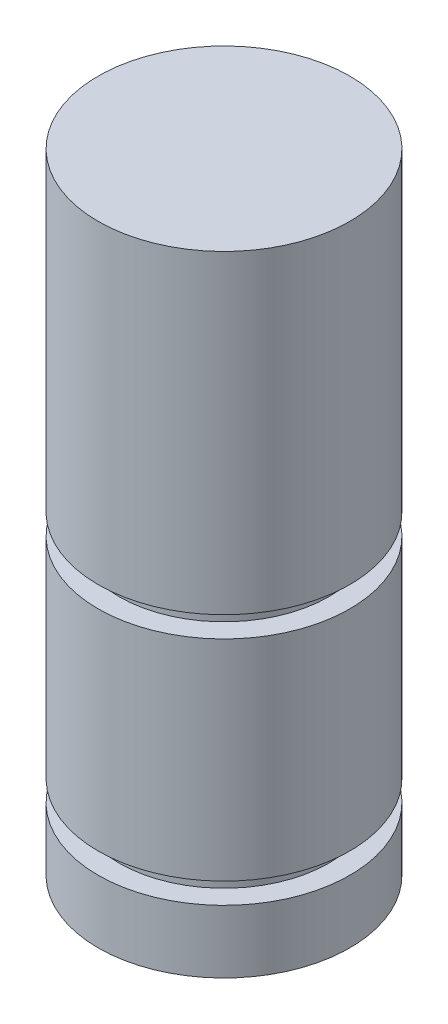
SolidWorks part; units mm, degrees
ref_plane "Front Plane" through (0, 0, 0) normal (0, 0, 1) x (1, 0, 0)
ref_plane "Top Plane" through (0, 0, 0) normal (0, 1, 0) x (1, 0, 0)
ref_plane "Right Plane" through (0, 0, 0) normal (1, 0, 0) x (0, 0, -1)
sketch "Sketch1" plane through (0, 0, 0) normal (0, 1, 0) x (1, 0, 0)
  circle A0 centre (0, 0) radius 6
  dimension "D1" = 12
extrude "Boss-Extrude1" add sketch "Sketch1" along normal blind 30 contours A0
sketch "Sketch2" plane through (0, 0, 0) normal (0, -1, 0) x (1, 0, 0)
  circle A0 centre (0, 0) radius 1.95
  dimension "D1" = 3.9
extrude "Cut-Extrude1" cut sketch "Sketch2" against normal blind 10
ref_plane "Plane1" through (0, 14, 0) normal (0, -1, 0) x (-1, 0, 0)
ref_plane "Plane2" through (0, 4, 0) normal (0, -1, 0) x (-1, 0, 0)
sketch "Sketch3" plane through (0, 14, 0) normal (0, -1, 0) x (-1, 0, 0)
  circle A0 centre (0, 0) radius 6 construction
  circle A1 centre (0, 0) radius 6
  circle A2 centre (0, 0) radius 5
  dimension "D1" = 1
extrude "Cut-Extrude2" cut sketch "Sketch3" against normal blind 1
sketch "Sketch4" plane through (0, 4, 0) normal (0, -1, 0) x (-1, 0, 0)
  circle A0 centre (0, 0) radius 6 construction
  circle A1 centre (0, 0) radius 6
  circle A2 centre (0, 0) radius 5
  dimension "D1" = 10
extrude "Cut-Extrude3" cut sketch "Sketch4" along normal blind 1
